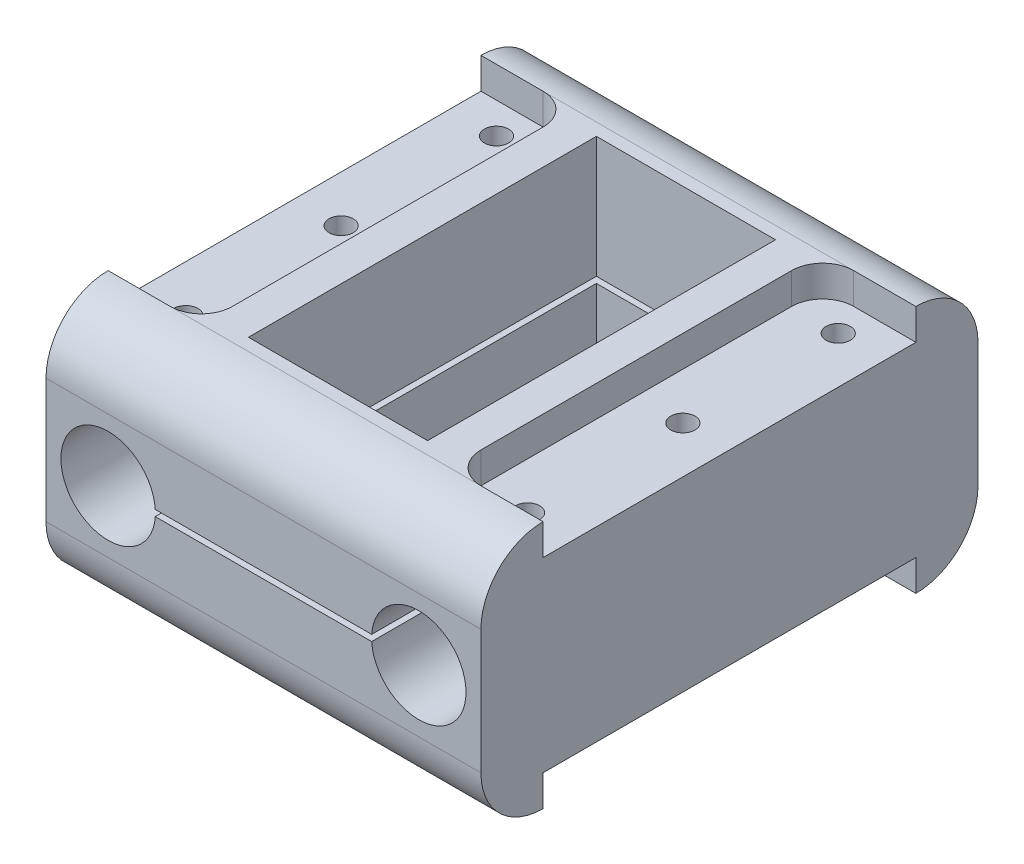
SolidWorks part; units mm, degrees
ref_plane "Front Plane" through (0, 0, 0) normal (0, 0, 1) x (1, 0, 0)
ref_plane "Top Plane" through (0, 0, 0) normal (0, 1, 0) x (1, 0, 0)
ref_plane "Right Plane" through (0, 0, 0) normal (1, 0, 0) x (0, 0, -1)
sketch "Sketch1" plane through (0, 0, 0) normal (0, 0, 1) x (1, 0, 0)
  line L0 (0, 0) -> (50, 0) construction
  line L2 (-10, 20) -> (60, 20)
  line L3 (-10, 20) -> (-10, -20)
  line L4 (-10, -20) -> (60, -20)
  line L5 (60, 20) -> (60, -20)
  line L6 (-10, 20) -> (60, -20) construction
  line L7 (-10, -20) -> (60, 20) construction
  circle A0 centre (0, 0) radius 7.6
  circle A1 centre (50, 0) radius 7.6
  point P5 (25, 0)
  dimension "D1" = 15.2
  dimension "D2" = 50
  dimension "D3" = 70
  dimension "D4" = 40
extrude "Boss-Extrude1" add sketch "Sketch1" along normal blind 80
fillet "Fillet1" radius 10 4 edges at (25, 20, 80) (25, -20, 80) (25, -20, 0) (25, 20, 0)
sketch "Sketch12" plane through (0, 0, 80) normal (0, 0, 1) x (1, 0, 0)
  line L0 (7.6, 0) -> (42.4, 0)
  line L1 (7.6, 0) -> (3.1193, 0)
  line L2 (42.4, 0) -> (46.982, 0)
  circle A0 centre (0, 0) radius 7.6 construction
  circle A1 centre (50, 0) radius 7.6 construction
extrude "Cut-Extrude-Thin1" cut sketch "Sketch12" against normal blind 95 and the other way through all thin thin type mid plane wall 1
sketch "Sketch21" plane through (-10, 0, 0) normal (-1, 0, 0) x (0, 0, 1)
  circle A0 centre (10, -14) radius 1.95
  circle A1 centre (70, -14) radius 1.95
  dimension "D1" = 3.9
  dimension "D2" = 3.9
  dimension "D3" = 6
  dimension "D4" = 6
sketch "Sketch24" plane through (0, 0.5, 0) normal (0, -1, 0) x (1, 0, 0)
  line L1 (10.5835, 68) -> (10.5835, 12)
  line L3 (39.4165, 12) -> (39.4165, 68)
  line L4 (7.5835, 80) -> (7.5835, 0)
  line L5 (7.5835, 0) -> (42.4165, 0)
  line L6 (42.4165, 0) -> (42.4165, 80)
  line L7 (42.4165, 80) -> (7.5835, 80)
  line L8 (7.5835, 80) -> (7.5835, 0)
  line L9 (7.5835, 0) -> (42.4165, 0)
  line L10 (42.4165, 0) -> (42.4165, 80)
  line L11 (42.4165, 80) -> (7.5835, 80)
  line L12 (10.5835, 68) -> (39.4165, 68)
  line L13 (10.5835, 12) -> (39.4165, 12)
  line L14 (10.5835, 77) -> (10.5835, 3) construction
  line L15 (39.4165, 3) -> (39.4165, 77) construction
  line L16 (39.4165, 77) -> (10.5835, 77) construction
  line L17 (10.5835, 3) -> (39.4165, 3) construction
  dimension "D3" = 12
  dimension "D4" = 12
  dimension "D1" = 0
  dimension "D2" = 3
extrude "Cut-Extrude15" cut sketch "Sketch24" against normal blind 40 and the other way blind 39 contours L3 L1 region at (25, 0.5, 40)
sketch "Sketch27" plane through (0, 20, 0) normal (0, 1, 0) x (1, 0, 0)
  line L0 (-10, -70) -> (60, -70) construction
  line L1 (-10, -10) -> (0, -10)
  line L2 (-10, -10) -> (-10, -70)
  line L3 (-10, -70) -> (0, -70)
  line L4 (5, -15) -> (5, -65)
  arc A0 (0, -70) -> (5, -65) centre (0, -65) ccw
  arc A1 (0, -10) -> (5, -15) centre (0, -15) cw
  point P9 (5, -70)
  point P12 (5, -10)
  dimension "D2" = 5
  dimension "D1" = 15
extrude "Cut-Extrude17" cut sketch "Sketch27" against normal blind 5
sketch "Sketch28" plane through (0, 15, 0) normal (0, 1, 0) x (1, 0, 0)
  line L0 (5, -15) -> (-2.5, -15) construction
  line L1 (5, -40) -> (-2.5, -40) construction
  line L2 (5, -65) -> (5, -15) construction
  line L3 (5, -65) -> (-2.5, -65) construction
  circle A0 centre (-2.5, -15) radius 1.95
  circle A1 centre (-2.5, -40) radius 1.95
  circle A2 centre (-2.5, -65) radius 1.95
  dimension "D2" = 3.9
  dimension "D1" = 7.5
extrude "Cut-Extrude18" cut sketch "Sketch28" against normal blind 20
ref_plane "Plane2" through (25, 0, 0) normal (-1, 0, 0) x (0, 0, 1)
mirror "Mirror1" about plane through (25, 0, 0) normal (-1, 0, 0) of "Cut-Extrude17", "Cut-Extrude18"
mirror "Mirror2" about plane through (0, 0, 0) normal (0, 1, 0) of "Mirror1"
